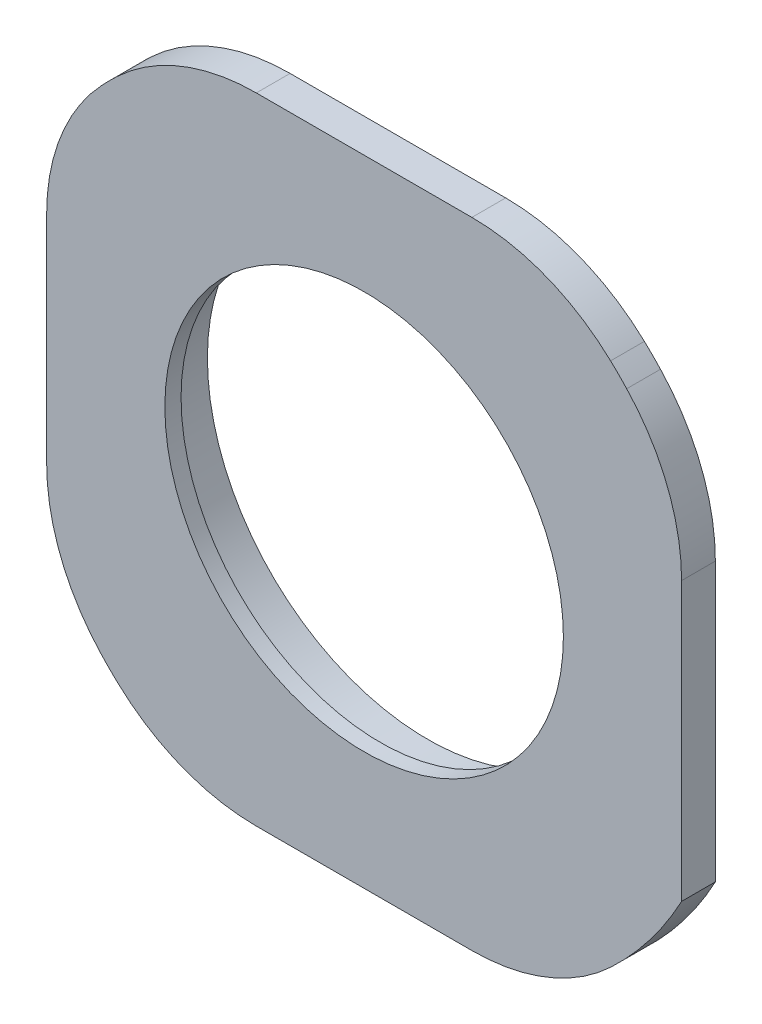
SolidWorks part; units mm, degrees
ref_plane "Front Plane" through (0, 0, 0) normal (0, 0, 1) x (1, 0, 0)
ref_plane "Top Plane" through (0, 0, 0) normal (0, 1, 0) x (1, 0, 0)
ref_plane "Right Plane" through (0, 0, 0) normal (1, 0, 0) x (0, 0, -1)
sketch "Sketch1" plane through (0, 0, 0) normal (0, 0, 1) x (1, 0, 0)
  line L4 (-47, 15.9577) -> (-47, -15.9577)
  line L5 (-15.9577, -47) -> (15.9577, -47)
  line L6 (47, -25.1719) -> (47, 15.9577)
  line L7 (15.9577, 47) -> (-15.9577, 47)
  circle A1 centre (0, 0) radius 36
  arc A2 (32.6244, 15.22) -> (34.2676, 11.0331) centre (33.5115, 13.1523) ccw
  arc A4 (26.6888, 24.1601) -> (29.4931, 20.6435) centre (28.1459, 22.4456) ccw
  arc A6 (18.3818, 30.9534) -> (22.098, 28.4196) centre (20.2795, 29.7446) ccw
  arc A8 (8.4415, 34.9963) -> (12.7395, 33.6706) centre (10.6112, 34.4006) ccw
  arc A10 (-2.2489, 35.9297) -> (2.2489, 35.9297) centre (0, 36) ccw
  arc A12 (-12.7395, 33.6706) -> (-8.4415, 34.9963) centre (-10.6112, 34.4006) ccw
  arc A14 (-22.098, 28.4196) -> (-18.3818, 30.9534) centre (-20.2795, 29.7446) ccw
  arc A16 (-29.4931, 20.6435) -> (-26.6888, 24.1601) centre (-28.1459, 22.4456) ccw
  arc A18 (-34.2676, 11.0331) -> (-32.6244, 15.22) centre (-33.5115, 13.1523) ccw
  arc A20 (-35.9973, 0.4424) -> (-35.6612, 4.9276) centre (-35.8993, 2.6903) ccw
  arc A22 (-34.5284, -10.1876) -> (-35.5293, -5.8026) centre (-35.0974, -8.0108) ccw
  arc A24 (-29.9916, -19.9124) -> (-32.2405, -16.0172) centre (-31.1769, -18) ccw
  arc A26 (-22.7898, -27.868) -> (-26.087, -24.8087) centre (-24.4862, -26.3899) ccw
  arc A28 (-13.5631, -33.3473) -> (-17.6155, -31.3958) centre (-15.6198, -32.4349) ccw
  arc A30 (-3.1313, -35.8636) -> (-7.5788, -35.1932) centre (-5.3655, -35.5979) ccw
  arc A32 (7.5788, -35.1932) -> (3.1313, -35.8636) centre (5.3655, -35.5979) ccw
  arc A34 (17.6155, -31.3958) -> (13.5631, -33.3473) centre (15.6198, -32.4349) ccw
  arc A36 (26.087, -24.8087) -> (22.7898, -27.868) centre (24.4862, -26.3899) ccw
  arc A38 (32.2405, -16.0172) -> (29.9916, -19.9124) centre (31.1769, -18) ccw
  arc A40 (35.5293, -5.8026) -> (34.5284, -10.1876) centre (35.0974, -8.0108) ccw
  arc A42 (35.6612, 4.9276) -> (35.9973, 0.4424) centre (35.8993, 2.6903) ccw
  arc A46 (32.7, 0) -> (-32.7, 0) centre (0, 0) ccw
  arc A47 (-32.7, 0) -> (32.7, 0) centre (0, 0) ccw
  arc A225 (-36.4898, 38.8731) -> (-38.8731, 36.4898) centre (0, 0) ccw
  arc A226 (-38.8731, 36.4898) -> (-47, 15.9577) centre (-17, 15.9577) ccw
  arc A227 (-47, -15.9577) -> (-38.8731, -36.4898) centre (-17, -15.9577) ccw
  arc A228 (-38.8731, -36.4898) -> (-36.4898, -38.8731) centre (0, 0) ccw
  arc A229 (-36.4898, -38.8731) -> (-15.9577, -47) centre (-15.9577, -17) ccw
  arc A230 (15.9577, -47) -> (36.4898, -38.8731) centre (15.9577, -17) ccw
  arc A231 (36.4898, -38.8731) -> (47, -25.1719) centre (0, 0) ccw
  arc A232 (47, 15.9577) -> (38.8731, 36.4898) centre (17, 15.9577) ccw
  arc A233 (38.8731, 36.4898) -> (36.4898, 38.8731) centre (0, 0) ccw
  arc A234 (36.4898, 38.8731) -> (15.9577, 47) centre (15.9577, 17) ccw
  arc A235 (-15.9577, 47) -> (-36.4898, 38.8731) centre (-15.9577, 17) ccw
extrude "Boss-Extrude1" add sketch "Sketch1" along normal blind 5 contours L7 A235 A225 A226 L4 A227 A228 A229 L5 A230 A231 L6 A232 A233 A234 A1 | A42 A1 A2 A4 A6 A8 A10 A12 A14 A16 A18 A20 A22 A24 A26 A28 A30 A32 A34 A36 A38 A40 A47 A46 | A46 A47 region at (-43.6583, 26.5094, 0) region at (34.8677, -2.8285, 0) region at (0, 0, 0)
extrude "Boss-Extrude2" add sketch "Sketch1<4>" against normal offset from surface (4.4 mm away) 0.2 contours A42 A1 A2 A4 A6 A8 A10 A12 A14 A16 A18 A20 A22 A24 A26 A28 A30 A32 A34 A36 A38 A40 A47 A46 region at (34.8677, -2.8285, 0)
sketch "Sketch1<4>" plane through (0, 0, 0) normal (0, 0, 1) x (1, 0, 0) same geometry as "Sketch1"
sketch "Sketch2" plane through (0, 0, 5) normal (0, 0, 1) x (1, 0, 0)
  line L4 (15.9577, 47) -> (-15.9577, 47)
  line L5 (-47, 15.9577) -> (-47, -15.9577)
  line L6 (-15.9577, -47) -> (15.9577, -47)
  line L7 (47, -25.1719) -> (47, 15.9577)
  line L8 (15.9577, 47) -> (-15.9577, 47)
  line L9 (-47, 15.9577) -> (-47, -15.9577)
  line L10 (-15.9577, -47) -> (15.9577, -47)
  line L11 (47, -25.1719) -> (47, 15.9577)
  arc A11 (-15.9577, 47) -> (-36.4898, 38.8731) centre (-15.9577, 17) ccw
  arc A12 (-36.4898, 38.8731) -> (-38.8731, 36.4898) centre (0, 0) ccw
  arc A13 (-38.8731, 36.4898) -> (-47, 15.9577) centre (-17, 15.9577) ccw
  arc A14 (-47, -15.9577) -> (-38.8731, -36.4898) centre (-17, -15.9577) ccw
  arc A15 (-38.8731, -36.4898) -> (-36.4898, -38.8731) centre (0, 0) ccw
  arc A16 (-36.4898, -38.8731) -> (-15.9577, -47) centre (-15.9577, -17) ccw
  arc A17 (15.9577, -47) -> (36.4898, -38.8731) centre (15.9577, -17) ccw
  arc A18 (36.4898, -38.8731) -> (47, -25.1719) centre (0, 0) ccw
  arc A19 (47, 15.9577) -> (38.8731, 36.4898) centre (17, 15.9577) ccw
  arc A20 (38.8731, 36.4898) -> (36.4898, 38.8731) centre (0, 0) ccw
  arc A21 (36.4898, 38.8731) -> (15.9577, 47) centre (15.9577, 17) ccw
  arc A22 (-15.9577, 47) -> (-36.4898, 38.8731) centre (-15.9577, 17) ccw
  arc A23 (-36.4898, 38.8731) -> (-38.8731, 36.4898) centre (0, 0) ccw
  arc A24 (-38.8731, 36.4898) -> (-47, 15.9577) centre (-17, 15.9577) ccw
  arc A25 (-47, -15.9577) -> (-38.8731, -36.4898) centre (-17, -15.9577) ccw
  arc A26 (-38.8731, -36.4898) -> (-36.4898, -38.8731) centre (0, 0) ccw
  arc A27 (-36.4898, -38.8731) -> (-15.9577, -47) centre (-15.9577, -17) ccw
  arc A28 (15.9577, -47) -> (36.4898, -38.8731) centre (15.9577, -17) ccw
  arc A29 (36.4898, -38.8731) -> (47, -25.1719) centre (0, 0) ccw
  arc A30 (47, 15.9577) -> (38.8731, 36.4898) centre (17, 15.9577) ccw
  arc A31 (38.8731, 36.4898) -> (36.4898, 38.8731) centre (0, 0) ccw
  arc A32 (36.4898, 38.8731) -> (15.9577, 47) centre (15.9577, 17) ccw
  dimension "D1" = 0
extrude "Boss-Extrude3" add sketch "Sketch2" against normal up to surface (5 mm away) up to face at (0, 0, 0)
sketch "Sketch3" plane through (0, 0, 0) normal (0, 0, -1) x (-1, 0, 0)
  circle A0 centre (0, 0) radius 32.6
  circle A1 centre (0, 0) radius 32.7
  circle A2 centre (0, 0) radius 32.7
  dimension "D1" = 0
  dimension "D2" = 0.1
extrude "Boss-Extrude4" add sketch "Sketch3" along normal up to surface (4.4 mm away) up to face at (0, 0, -4.4)
sketch "Sketch4" plane through (0, 0, 5) normal (0, 0, 1) x (1, 0, 0)
  line L4 (15.9577, 47) -> (-15.9577, 47)
  line L5 (-47, 15.9577) -> (-47, -15.9577)
  line L6 (-15.9577, -47) -> (15.9577, -47)
  line L7 (47, -25.1719) -> (47, 15.9577)
  line L8 (15.9577, 47) -> (-15.9577, 47)
  line L9 (-47, 15.9577) -> (-47, -15.9577)
  line L10 (-15.9577, -47) -> (15.9577, -47)
  line L11 (47, -25.1719) -> (47, 15.9577)
  circle A0 centre (0, 0) radius 32.6
  arc A11 (-15.9577, 47) -> (-36.4898, 38.8731) centre (-15.9577, 17) ccw
  arc A12 (-36.4898, 38.8731) -> (-38.8731, 36.4898) centre (0, 0) ccw
  arc A13 (-38.8731, 36.4898) -> (-47, 15.9577) centre (-17, 15.9577) ccw
  arc A14 (-47, -15.9577) -> (-38.8731, -36.4898) centre (-17, -15.9577) ccw
  arc A15 (-38.8731, -36.4898) -> (-36.4898, -38.8731) centre (0, 0) ccw
  arc A16 (-36.4898, -38.8731) -> (-15.9577, -47) centre (-15.9577, -17) ccw
  arc A17 (15.9577, -47) -> (36.4898, -38.8731) centre (15.9577, -17) ccw
  arc A18 (36.4898, -38.8731) -> (47, -25.1719) centre (0, 0) ccw
  arc A19 (47, 15.9577) -> (38.8731, 36.4898) centre (17, 15.9577) ccw
  arc A20 (38.8731, 36.4898) -> (36.4898, 38.8731) centre (0, 0) ccw
  arc A21 (36.4898, 38.8731) -> (15.9577, 47) centre (15.9577, 17) ccw
  arc A22 (-15.9577, 47) -> (-36.4898, 38.8731) centre (-15.9577, 17) ccw
  arc A23 (-36.4898, 38.8731) -> (-38.8731, 36.4898) centre (0, 0) ccw
  arc A24 (-38.8731, 36.4898) -> (-47, 15.9577) centre (-17, 15.9577) ccw
  arc A25 (-47, -15.9577) -> (-38.8731, -36.4898) centre (-17, -15.9577) ccw
  arc A26 (-38.8731, -36.4898) -> (-36.4898, -38.8731) centre (0, 0) ccw
  arc A27 (-36.4898, -38.8731) -> (-15.9577, -47) centre (-15.9577, -17) ccw
  arc A28 (15.9577, -47) -> (36.4898, -38.8731) centre (15.9577, -17) ccw
  arc A29 (36.4898, -38.8731) -> (47, -25.1719) centre (0, 0) ccw
  arc A30 (47, 15.9577) -> (38.8731, 36.4898) centre (17, 15.9577) ccw
  arc A31 (38.8731, 36.4898) -> (36.4898, 38.8731) centre (0, 0) ccw
  arc A32 (36.4898, 38.8731) -> (15.9577, 47) centre (15.9577, 17) ccw
  dimension "D2" = 65.2
  dimension "D1" = 0
extrude "Cut-Extrude1" cut sketch "Sketch4" against normal through all both contours A0 region at (0, 0, 5)
sketch "Sketch5" plane through (0, 0, 5) normal (0, 0, 1) x (1, 0, 0)
  line L4 (15.9577, 47) -> (-15.9577, 47)
  line L5 (-47, 15.9577) -> (-47, -15.9577)
  line L6 (-15.9577, -47) -> (15.9577, -47)
  line L7 (47, -25.1719) -> (47, 15.9577)
  line L8 (15.9577, 47) -> (-15.9577, 47)
  line L9 (-47, 15.9577) -> (-47, -15.9577)
  line L10 (-15.9577, -47) -> (15.9577, -47)
  line L11 (47, -25.1719) -> (47, 15.9577)
  circle A0 centre (0, 0) radius 29.5
  arc A12 (-15.9577, 47) -> (-36.4898, 38.8731) centre (-15.9577, 17) ccw
  arc A13 (-36.4898, 38.8731) -> (-38.8731, 36.4898) centre (0, 0) ccw
  arc A14 (-38.8731, 36.4898) -> (-47, 15.9577) centre (-17, 15.9577) ccw
  arc A15 (-47, -15.9577) -> (-38.8731, -36.4898) centre (-17, -15.9577) ccw
  arc A16 (-38.8731, -36.4898) -> (-36.4898, -38.8731) centre (0, 0) ccw
  arc A17 (-36.4898, -38.8731) -> (-15.9577, -47) centre (-15.9577, -17) ccw
  arc A18 (15.9577, -47) -> (36.4898, -38.8731) centre (15.9577, -17) ccw
  arc A19 (36.4898, -38.8731) -> (47, -25.1719) centre (0, 0) ccw
  arc A20 (47, 15.9577) -> (38.8731, 36.4898) centre (17, 15.9577) ccw
  arc A21 (38.8731, 36.4898) -> (36.4898, 38.8731) centre (0, 0) ccw
  arc A22 (36.4898, 38.8731) -> (15.9577, 47) centre (15.9577, 17) ccw
  arc A23 (-15.9577, 47) -> (-36.4898, 38.8731) centre (-15.9577, 17) ccw
  arc A24 (-36.4898, 38.8731) -> (-38.8731, 36.4898) centre (0, 0) ccw
  arc A25 (-38.8731, 36.4898) -> (-47, 15.9577) centre (-17, 15.9577) ccw
  arc A26 (-47, -15.9577) -> (-38.8731, -36.4898) centre (-17, -15.9577) ccw
  arc A27 (-38.8731, -36.4898) -> (-36.4898, -38.8731) centre (0, 0) ccw
  arc A28 (-36.4898, -38.8731) -> (-15.9577, -47) centre (-15.9577, -17) ccw
  arc A29 (15.9577, -47) -> (36.4898, -38.8731) centre (15.9577, -17) ccw
  arc A30 (36.4898, -38.8731) -> (47, -25.1719) centre (0, 0) ccw
  arc A31 (47, 15.9577) -> (38.8731, 36.4898) centre (17, 15.9577) ccw
  arc A32 (38.8731, 36.4898) -> (36.4898, 38.8731) centre (0, 0) ccw
  arc A33 (36.4898, 38.8731) -> (15.9577, 47) centre (15.9577, 17) ccw
  dimension "D1" = 59
  dimension "D2" = 0
extrude "Boss-Extrude5" add sketch "Sketch5" against normal offset from surface (2.4 mm away) 7 up to face at (0, 0, -4.4)
